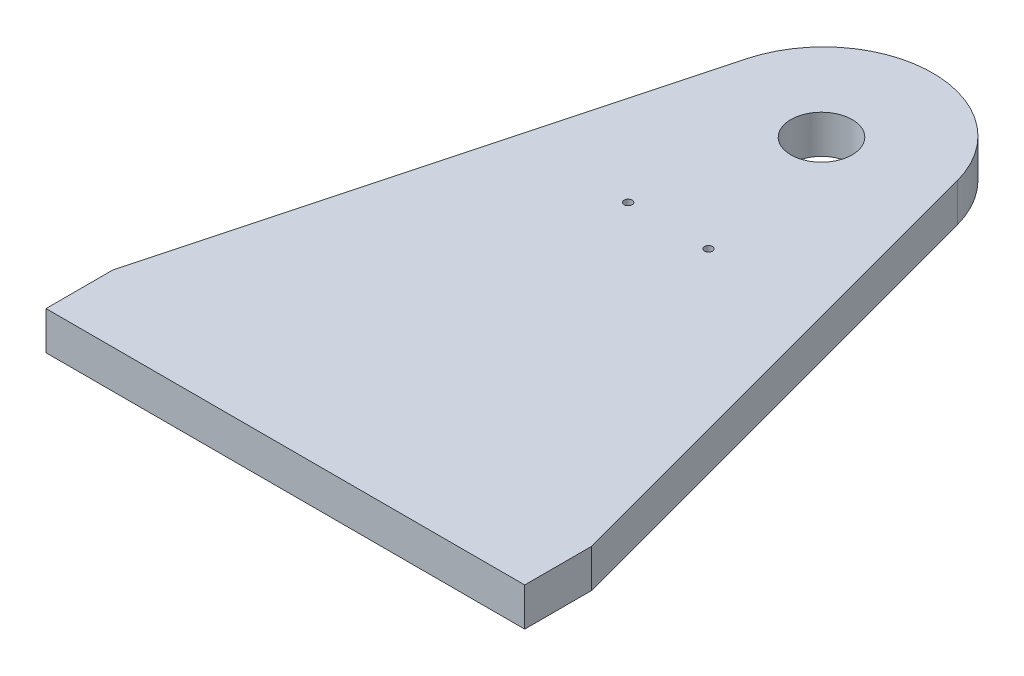
SolidWorks part; units mm, degrees
material "PTFE (general)"
ref_plane "Front Plane" through (0, 0, 0) normal (0, 0, 1) x (1, 0, 0)
ref_plane "Top Plane" through (0, 0, 0) normal (0, 1, 0) x (1, 0, 0)
ref_plane "Right Plane" through (0, 0, 0) normal (1, 0, 0) x (0, 0, -1)
sketch "Sketch1" plane through (0, 0, 0) normal (0, 1, 0) x (1, 0, 0)
  line L0 (-55.1189, 295.8) -> (-125, 35)
  line L1 (-125, 35) -> (-125, 0)
  line L2 (-125, 0) -> (125, 0)
  line L3 (125, 0) -> (125, 35)
  line L5 (125, 35) -> (55.1189, 295.8)
  arc A0 (-55.1189, 295.8) -> (55.1189, 295.8) centre (0, 281.0309) cw
  point P2 (0, 0)
  dimension "D1" = 35
  dimension "D2" = 250
  dimension "D3" = 195
  dimension "D4" = 270
  dimension "D5" = 195
  dimension "D6" = 270
extrude "Boss-Extrude1" add sketch "Sketch1" along normal blind 20
sketch "Sketch3" plane through (0, 20, 0) normal (0, 1, 0) x (1, 0, 0)
  line L0 (0, 0) -> (0, 338.0942) construction
  line L1 (-50.4531, 200) -> (50.0066, 200) construction
  line L2 (0, 280) -> (48.5342, 280) construction
  line L3 (-125, 0) -> (125, 0) construction
  arc A0 (55.1189, 295.8) -> (-55.1189, 295.8) centre (0, 281.0309) ccw construction
  circle A1 centre (-21, 200) radius 2.1
  circle A2 centre (21, 200) radius 2.1
  circle A3 centre (0, 280) radius 16
  dimension "D2" = 4.2
  dimension "D4" = 32
  dimension "D1" = 280
  dimension "D3" = 21
  dimension "D5" = 80
extrude "Cut-Extrude2" cut sketch "Sketch3" against normal up to surface (20 mm away) up to face at (0, 0, -117.3157)
